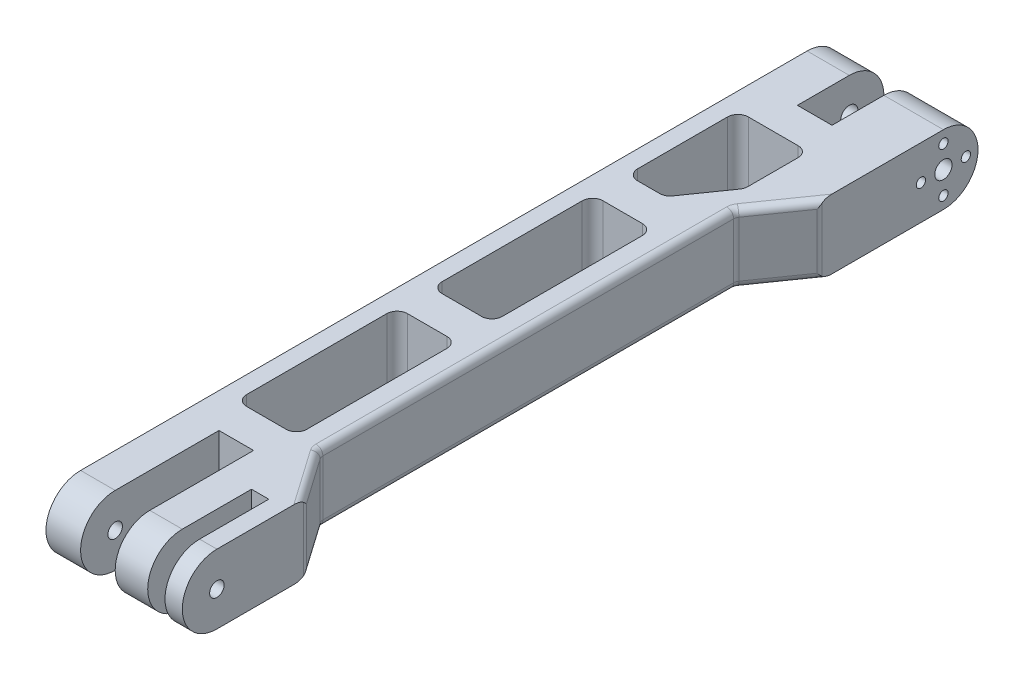
SolidWorks part; units mm, degrees
ref_plane "前视基准面" through (0, 0, 0) normal (0, 0, 1) x (1, 0, 0)
ref_plane "上视基准面" through (0, 0, 0) normal (0, 1, 0) x (1, 0, 0)
ref_plane "右视基准面" through (0, 0, 0) normal (1, 0, 0) x (0, 0, -1)
other "Configuration Table"
sketch "草图1" plane through (0, 0, 0) normal (0, 0, 1) x (1, 0, 0)
  line L1 (0, 0) -> (39.4, 0)
  line L2 (0, 0) -> (0, 20)
  line L3 (0, 20) -> (39.4, 20)
  line L4 (39.4, 0) -> (39.4, 20)
  dimension "D1" = 39.4
  dimension "D2" = 20
extrude "凸台-拉伸1" add sketch "草图1" along normal blind 230
fillet "圆角2" 2 edges at (19.7, 20, 0) (19.7, 0, 0) type full round first side face at (19.7, 20, 115) second side face at (19.7, 0, 115) middle face at (19.7, 10, 0)
sketch "草图2" plane through (0, 0, 0) normal (-1, 0, 0) x (0, 0, 1)
  circle A0 centre (10, 10) radius 2.5
  dimension "D1" = 5
extrude "切除-拉伸1" cut sketch "草图2" against normal through all
sketch "草图3" plane through (0, 0, 0) normal (0, -1, 0) x (-1, 0, 0)
  line L0 (0, 0) -> (-39.4, 0) construction
  line L1 (-12.2, 0) -> (-22.2, 0)
  line L2 (-12.2, 0) -> (-12.2, -25)
  line L3 (-12.2, -25) -> (-22.2, -25)
  line L4 (-22.2, 0) -> (-22.2, -25)
  line L5 (0, -230) -> (0, -10) construction
  line L7 (-39.4, -230) -> (-39.4, -10) construction
  dimension "D1" = 12.2
  dimension "D2" = 17.2
  dimension "D3" = 25
extrude "切除-拉伸2" cut sketch "草图3" against normal through all
sketch "草图4" plane through (39.4, 0, 0) normal (1, 0, 0) x (0, 0, -1)
  line L0 (-16.5, 10) -> (-3.5, 10) construction
  line L1 (-10, 16.5) -> (-10, 3.5) construction
  circle A0 centre (-10, 10) radius 6.5 construction
  circle A1 centre (-3.5, 10) radius 1.35
  circle A2 centre (-10, 16.5) radius 1.35
  circle A3 centre (-16.5, 10) radius 1.35
  circle A4 centre (-10, 3.5) radius 1.35
  dimension "D1" = 13
  dimension "D2" = 2.7
extrude "切除-拉伸3" cut sketch "草图4" against normal blind 20
sketch "草图5" plane through (0, 0, 0) normal (0, -1, 0) x (-1, 0, 0)
  line L0 (-39.4, -45.7185) -> (-29.4, -60)
  line L1 (-39.4, -230) -> (-39.4, -10) construction
  line L2 (-29.4, -60) -> (-29.4, -180)
  line L3 (-29.4, -180) -> (-39.4, -194.2815)
  line L4 (-29.4, -120) -> (-39.4, -120) construction
  line L5 (-22.2, 0) -> (-39.4, 0) construction
  line L6 (-39.4, -194.2815) -> (-39.4, -45.7185)
  dimension "D1" = 145
  dimension "D2" = 10
  dimension "D3" = 120
  dimension "D4" = 120
extrude "切除-拉伸4" cut sketch "草图5" against normal through all
fillet "圆角4" radius 2 10 edges at (34.4, 20, 187.1407) (34.4, 0, 187.1407) (34.4, 20, 52.8593) (34.4, 0, 52.8593) (29.4, 10, 180) (29.4, 20, 120) (29.4, 10, 60) (29.4, 0, 120) (39.4, 10, 194.2815) (39.4, 10, 45.7185)
fillet "圆角5" 2 edges at (19.7, 20, 230) (19.7, 0, 230) type full round first side face at (24.0781, 20, 90.7143) second side face at (24.0781, 0, 90.7143) middle face at (19.7, 10, 230)
sketch "草图6" plane through (0, 0, 0) normal (-1, 0, 0) x (0, 0, 1)
  circle A0 centre (220, 10) radius 2.1
  dimension "D1" = 4.2
extrude "切除-拉伸5" cut sketch "草图6" against normal through all
sketch "草图7" plane through (0, 0, 0) normal (0, -1, 0) x (-1, 0, 0)
  line L0 (-39.4, -230) -> (0, -230) construction
  line L1 (-10, -230) -> (-20, -230)
  line L2 (-10, -230) -> (-10, -190)
  line L3 (-10, -190) -> (-20, -190)
  line L4 (-20, -230) -> (-20, -190)
  line L5 (0, -220) -> (0, -10) construction
  dimension "D1" = 10
  dimension "D2" = 10
  dimension "D3" = 40
extrude "切除-拉伸6" cut sketch "草图7" against normal through all
sketch "草图8" plane through (0, 0, 0) normal (0, -1, 0) x (-1, 0, 0)
  line L0 (-5, -64) -> (-5, -38)
  line L1 (-8, -35) -> (-22.4, -35)
  line L2 (-25.4, -38) -> (-25.4, -52.5626)
  line L3 (-24.8575, -54.2833) -> (-16.8489, -65.7207)
  line L4 (-14.3914, -67) -> (-8, -67)
  line L5 (-22.2, -25) -> (-12.2, -25) construction
  line L6 (0, -220) -> (0, -10) construction
  line L7 (-39.4, -42.2316) -> (-39.4, -10) construction
  line L8 (-39.4, -42.2316) -> (-28.1234, -58.3363) construction
  line L18 (-27.4, -60.6306) -> (-27.4, -179.3694) construction
  line L19 (-8, -77) -> (-19.4, -77)
  line L20 (-5, -80) -> (-5, -120.5)
  line L21 (-8, -123.5) -> (-19.4, -123.5)
  line L22 (-22.4, -80) -> (-22.4, -120.5)
  line L23 (-8, -133.5) -> (-19.4, -133.5)
  line L24 (-5, -136.5) -> (-5, -177)
  line L25 (-8, -180) -> (-19.4, -180)
  line L26 (-22.4, -136.5) -> (-22.4, -177)
  line L27 (-10, -190) -> (-20, -190) construction
  arc A0 (-5, -177) -> (-8, -180) centre (-8, -177) cw
  arc A1 (-19.4, -180) -> (-22.4, -177) centre (-19.4, -177) cw
  arc A2 (-19.4, -133.5) -> (-22.4, -136.5) centre (-19.4, -136.5) ccw
  arc A3 (-8, -133.5) -> (-5, -136.5) centre (-8, -136.5) cw
  arc A4 (-5, -120.5) -> (-8, -123.5) centre (-8, -120.5) cw
  arc A5 (-19.4, -123.5) -> (-22.4, -120.5) centre (-19.4, -120.5) cw
  arc A6 (-19.4, -77) -> (-22.4, -80) centre (-19.4, -80) ccw
  arc A7 (-8, -77) -> (-5, -80) centre (-8, -80) cw
  arc A8 (-5, -38) -> (-8, -35) centre (-8, -38) ccw
  arc A9 (-22.4, -35) -> (-25.4, -38) centre (-22.4, -38) ccw
  arc A10 (-25.4, -52.5626) -> (-24.8575, -54.2833) centre (-22.4, -52.5626) ccw
  arc A11 (-16.8489, -65.7207) -> (-14.3914, -67) centre (-14.3914, -64) ccw
  arc A12 (-5, -64) -> (-8, -67) centre (-8, -64) cw
  point P23 (-11.1957, -67)
  dimension "D13" = 3
  dimension "D1" = 10
  dimension "D2" = 5
  dimension "D3" = 14
  dimension "D4" = 32
  dimension "D5" = 5
  dimension "D6" = 5
  dimension "D7" = 5
  dimension "D8" = 5
  dimension "D9" = 5
  dimension "D10" = 10
  dimension "D11" = 10
  dimension "D12" = 10
extrude "切除-拉伸7" cut sketch "草图8" against normal through all
sketch "草图9" plane through (0, 0, 0) normal (0, -1, 0) x (-1, 0, 0)
  line L0 (-39.4, -230) -> (-20, -230) construction
  line L1 (-29.4, -230) -> (-34.4, -230)
  line L2 (-29.4, -230) -> (-29.4, -200)
  line L3 (-29.4, -200) -> (-34.4, -200)
  line L4 (-34.4, -230) -> (-34.4, -200)
  line L8 (-39.4, -220) -> (-39.4, -197.7684) construction
  dimension "D1" = 5
  dimension "D2" = 5
  dimension "D3" = 30
extrude "切除-拉伸8" cut sketch "草图9" against normal through all
